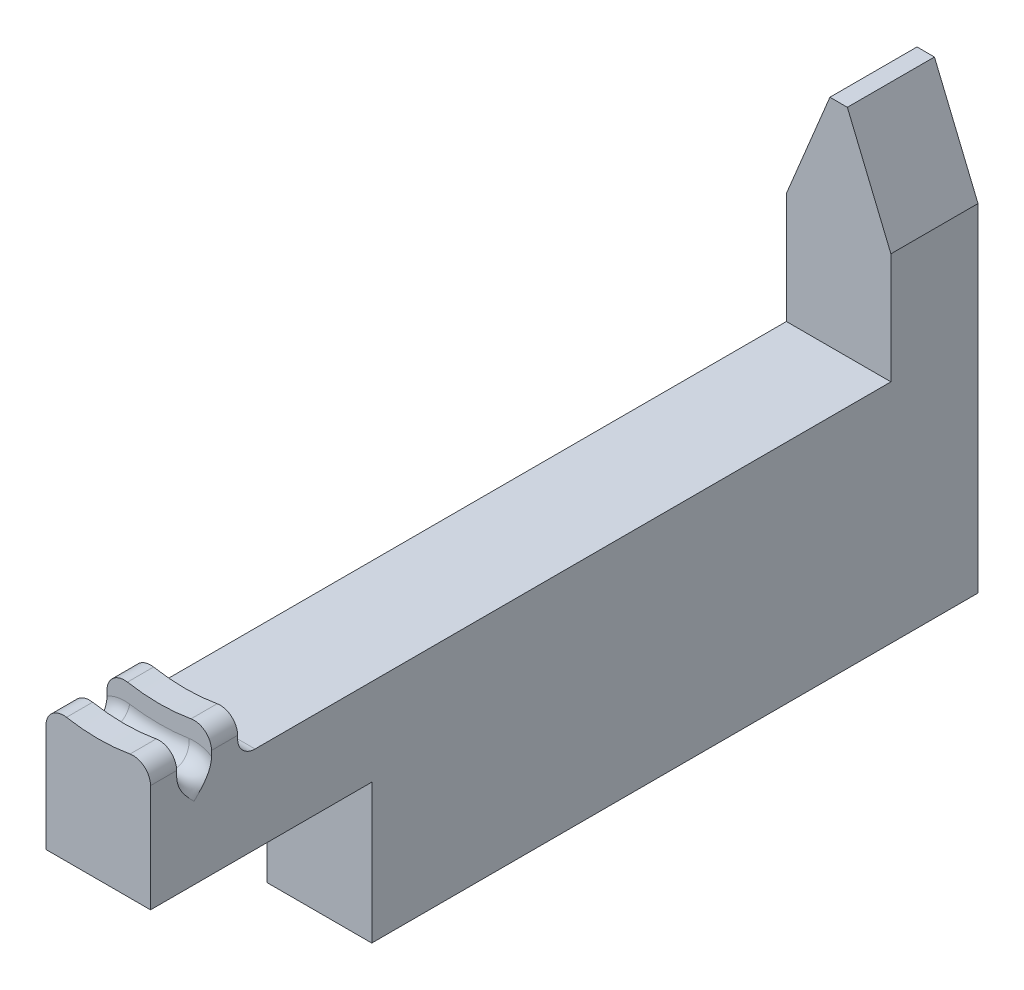
SolidWorks part; units mm, degrees
ref_plane "Front Plane" through (0, 0, 0) normal (0, 0, 1) x (1, 0, 0)
ref_plane "Top Plane" through (0, 0, 0) normal (0, 1, 0) x (1, 0, 0)
ref_plane "Right Plane" through (0, 0, 0) normal (1, 0, 0) x (0, 0, -1)
sketch "Sketch1" plane through (0, 0, 0) normal (0, 0, 1) x (1, 0, 0)
  line L0 (0, 12.4) -> (0, 0) construction
  circle A0 centre (0, 12.4) radius 12.4
  point P4 (0, 0)
  dimension "D1" = 24.8
sketch "Sketch2" plane through (0, 0, 0) normal (1, 0, 0) x (0, 0, -1)
  line L0 (0, 0) -> (40, 0)
  line L1 (40, 0) -> (40, 12.4)
  line L2 (0, 12.4) -> (40, 12.4) construction
  line L3 (0, 24.8) -> (0, 0) construction
  line L5 (0, -5) -> (45, -5)
  line L6 (45, -5) -> (45, 12.4)
  line L7 (45, 12.4) -> (40, 12.4)
  line L10 (0, 0) -> (0, -5)
  dimension "D1" = 40
  dimension "D2" = 5
  dimension "D3" = 5
extrude "Boss-Extrude1" add sketch "Sketch2" along normal mid plane 6
sketch "Sketch3" plane through (0, 0, 0) normal (0, 0, 1) x (1, 0, 0)
  line L4 (-3, 0) -> (-3, -5)
  line L5 (-3, -5) -> (3, -5)
  line L6 (3, -5) -> (3, 0)
  line L7 (3, 0) -> (-3, 0)
  line L8 (-3, 2.4421) -> (-3, -5)
  line L9 (-3, -5) -> (3, -5)
  line L10 (3, -5) -> (3, 2.4421)
  circle A0 centre (0, 12.4) radius 12.4 construction
  arc A1 (-3, 0.3684) -> (3, 0.3684) centre (0, 12.4) ccw construction
  arc A2 (-3, 2.4421) -> (3, 2.4421) centre (0, 12.4) ccw
  arc A3 (-6.2903, 4.118) -> (6.2903, 4.118) centre (0, 12.4) ccw construction
  arc A4 (-7.5, 2.5253) -> (7.5, 2.5253) centre (0, 12.4) ccw construction
  point P11 (-9.6125, 8.43)
  point P13 (6.2903, 4.118)
  point P14 (6.2903, 4.118)
  point P15 (6.2903, 4.118)
  point P16 (7.5, 2.5253)
  point P17 (-7.5, 2.5253)
  point P21 (7.5, 5.3457)
  dimension "D1" = 0
  dimension "D2" = 2
extrude "Boss-Extrude2" add sketch "Sketch3" along normal mid plane 5
sketch "Sketch4" plane through (0, 0, 0) normal (1, 0, 0) x (0, 0, -1)
  line L0 (-2.5, 2.4421) -> (2.5, 2.4421) construction
  line L1 (-1, 0) -> (1, 0)
  line L2 (-1, 0) -> (-1, 2.4421)
  line L3 (-1, 2.4421) -> (1, 2.4421)
  line L4 (1, 0) -> (1, 2.4421)
  line L5 (0, 12.4) -> (3.35, 12.4) construction
  line L6 (0, 24.8) -> (0, 0) construction
  dimension "D1" = 2
revolve "Cut-Revolve1" cut sketch "Sketch4" angle 360 about L5
fillet "Fillet1" radius 1 7 edges at (0, 0, -2.5) (3, 0.3684, 0) (-3, 0.3684, 0) (3, 2.4421, 1.75) (3, 2.4421, -1.75) (-3, 2.4421, -1.75) (-3, 2.4421, 1.75)
fillet "Fillet2" 2 edges at (0, 0, 1) (0, 0, -1) type full round first side face at (0, 0.7538, 1) second side face at (0, 0.7538, -1) middle face at (0, 0.0694, 0)
sketch "Sketch5" plane through (0, 0, -40) normal (0, 0, 1) x (1, 0, 0)
  line L6 (3, 6.3645) -> (0.5, 12.4)
  line L7 (-0.5, 12.4) -> (-3, 6.3645)
  line L10 (3, 12.4) -> (-3, 12.4) construction
  line L11 (0, 12.4) -> (0, 0) construction
  line L12 (-0.5, 12.4) -> (-3, 12.4)
  line L16 (-3, 12.4) -> (-3, 0)
  line L17 (-3, 0) -> (3, 0)
  line L18 (3, 0) -> (3, 12.4)
  line L19 (3, 12.4) -> (-3, 12.4)
  line L20 (-3, 12.4) -> (-3, 6.3645)
  line L22 (3, 6.3645) -> (3, 12.4)
  line L23 (3, 12.4) -> (0.5, 12.4)
  point P13 (0, 0)
  point P15 (0, 12.4)
  dimension "D1" = 6
  dimension "D2" = 45
  dimension "D3" = 1
  dimension "D4" = 0
extrude "Cut-Extrude2" cut sketch "Sketch5" against normal blind 5
sketch "Sketch6" plane through (0, 0, 0) normal (1, 0, 0) x (0, 0, -1)
  line L0 (-2.5, -5) -> (-2.5, 1.1768) construction
  line L1 (45, -5) -> (10.2, -5)
  line L2 (45, -5) -> (45, -13)
  line L3 (45, -13) -> (10.2, -13)
  line L4 (10.2, -5) -> (10.2, -13)
  dimension "D1" = 12.7
  dimension "D2" = 8
extrude "Boss-Extrude3" add sketch "Sketch6" along normal mid plane 6
